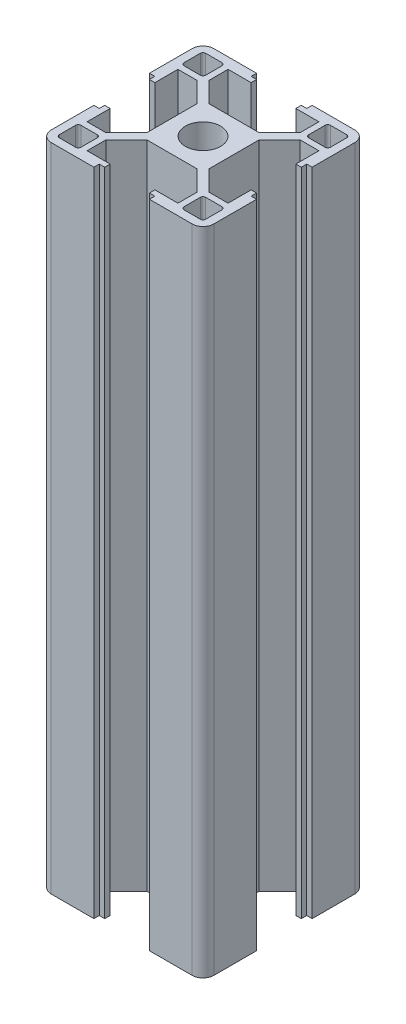
SolidWorks part; units mm, degrees
material "6061 Alloy"
ref_plane "Front Plane" through (0, 0, 0) normal (0, 0, 1) x (1, 0, 0)
ref_plane "Top Plane" through (0, 0, 0) normal (0, 1, 0) x (1, 0, 0)
ref_plane "Right Plane" through (0, 0, 0) normal (1, 0, 0) x (0, 0, -1)
sketch "Sketch1" plane through (0, 0, 0) normal (0, 1, 0) x (1, 0, 0)
  line L0 (-8.375, 13) -> (-4.125, 13)
  line L1 (-13, 15) -> (-4.125, 15)
  line L2 (-15, 13) -> (-15, 4.125)
  line L3 (-13, -15) -> (-4.125, -15)
  line L4 (15, 13) -> (15, 4.125)
  line L5 (-15, 15) -> (15, -15) construction
  line L6 (-15, -15) -> (15, 15) construction
  line L7 (-11.5, 11.5) -> (11.5, 11.5) construction
  line L8 (-11.5, 11.5) -> (-11.5, -11.5) construction
  line L9 (-11.5, -11.5) -> (11.5, -11.5) construction
  line L10 (11.5, 11.5) -> (11.5, -11.5) construction
  line L11 (-11.5, 11.5) -> (11.5, -11.5) construction
  line L12 (-11.5, -11.5) -> (11.5, 11.5) construction
  line L13 (-13.5, 13.5) -> (-9.5, 13.5)
  line L14 (-13.5, 13.5) -> (-13.5, 9.5)
  line L15 (-13.5, 9.5) -> (-9.5, 9.5)
  line L16 (-9.5, 13.5) -> (-9.5, 9.5)
  line L17 (-13.5, 13.5) -> (-9.5, 9.5) construction
  line L18 (-13.5, 9.5) -> (-9.5, 13.5) construction
  line L19 (13.5, 13.5) -> (9.5, 13.5)
  line L20 (13.5, 13.5) -> (13.5, 9.5)
  line L21 (13.5, 9.5) -> (9.5, 9.5)
  line L22 (9.5, 13.5) -> (9.5, 9.5)
  line L23 (13.5, 13.5) -> (9.5, 9.5) construction
  line L24 (13.5, 9.5) -> (9.5, 13.5) construction
  line L25 (13.5, -13.5) -> (9.5, -13.5)
  line L26 (13.5, -13.5) -> (13.5, -9.5)
  line L27 (13.5, -9.5) -> (9.5, -9.5)
  line L28 (9.5, -13.5) -> (9.5, -9.5)
  line L29 (13.5, -13.5) -> (9.5, -9.5) construction
  line L30 (13.5, -9.5) -> (9.5, -13.5) construction
  line L31 (-13.5, -13.5) -> (-9.5, -13.5)
  line L32 (-13.5, -13.5) -> (-13.5, -9.5)
  line L33 (-13.5, -9.5) -> (-9.5, -9.5)
  line L34 (-9.5, -13.5) -> (-9.5, -9.5)
  line L35 (-13.5, -13.5) -> (-9.5, -9.5) construction
  line L36 (-13.5, -9.5) -> (-9.5, -13.5) construction
  line L37 (0, 15) -> (0, 13) construction
  line L38 (-4.125, 15) -> (-4.125, 13)
  line L39 (4.125, 15) -> (4.125, 13)
  line L40 (4.125, 15) -> (13, 15)
  line L41 (-15, 15) -> (15, 15) construction
  line L42 (4.125, 13) -> (8.375, 13)
  line L43 (-15, 13) -> (15, 13) construction
  line L44 (8.375, 9.5064) -> (4.6186, 5.75)
  line L45 (-4.6186, -5.75) -> (4.6186, -5.75)
  line L46 (-8.375, 13) -> (-8.375, 9.5)
  line L47 (8.375, 13) -> (8.375, 9.5)
  line L48 (-8.375, 15) -> (-8.375, 13) construction
  line L49 (8.375, 15) -> (8.375, 13) construction
  line L50 (-5.75, -4.6186) -> (-5.75, 4.6186)
  line L51 (-4.6186, 5.75) -> (4.6186, 5.75)
  line L52 (5.75, -4.6186) -> (5.75, 4.6186)
  line L53 (-5.75, -5.75) -> (5.75, 5.75) construction
  line L54 (-5.75, 5.75) -> (5.75, -5.75) construction
  line L55 (-8.375, 9.5064) -> (-4.6186, 5.75)
  line L56 (-10.6314, 9.5) -> (-5.75, 4.6186)
  line L57 (-14.4343, 15.5657) -> (15.5657, -14.4343) construction
  line L58 (15, 4.125) -> (13, 4.125)
  line L59 (13, 8.375) -> (13, 4.125)
  line L60 (13, 8.375) -> (9.5, 8.375)
  line L61 (9.5064, 8.375) -> (5.75, 4.6186)
  line L62 (9.5064, -8.375) -> (5.75, -4.6186)
  line L63 (13, -8.375) -> (9.5, -8.375)
  line L64 (13, -4.125) -> (13, -8.375)
  line L65 (15, -4.125) -> (13, -4.125)
  line L66 (4.125, -15) -> (4.125, -13)
  line L67 (8.375, -13) -> (4.125, -13)
  line L68 (8.375, -13) -> (8.375, -9.5)
  line L69 (8.375, -9.5064) -> (4.6186, -5.75)
  line L70 (-8.375, -9.5064) -> (-4.6186, -5.75)
  line L71 (-8.375, -13) -> (-8.375, -9.5)
  line L72 (-4.125, -13) -> (-8.375, -13)
  line L73 (-4.125, -15) -> (-4.125, -13)
  line L74 (-15, -4.125) -> (-13, -4.125)
  line L75 (-13, -8.375) -> (-13, -4.125)
  line L76 (-13, -8.375) -> (-9.5, -8.375)
  line L77 (-9.5064, -8.375) -> (-5.75, -4.6186)
  line L78 (-9.5064, 8.375) -> (-5.75, 4.6186)
  line L79 (-13, 8.375) -> (-9.5, 8.375)
  line L80 (-13, 4.125) -> (-13, 8.375)
  line L81 (-15, 4.125) -> (-13, 4.125)
  line L82 (-15, -4.125) -> (-15, -13)
  line L83 (4.125, -15) -> (13, -15)
  line L84 (15, -4.125) -> (15, -13)
  circle A0 centre (0, 0) radius 3.25
  circle A1 centre (0, 0) radius 3.25
  circle A2 centre (0, 0) radius 3.25
  circle A3 centre (0, 0) radius 3.25
  arc A4 (-15, -13) -> (-13, -15) centre (-13, -13) ccw
  arc A5 (13, -15) -> (15, -13) centre (13, -13) ccw
  arc A6 (13, 15) -> (15, 13) centre (13, 13) cw
  arc A7 (-13, 15) -> (-15, 13) centre (-13, 13) ccw
  point P0 (0, 0)
  point P6 (0, 0)
  point P31 (0, 0)
  point P48 (-15.5657, 14.4343)
  point P49 (14.4343, -15.5657)
  point P60 (0, 5.75)
  point P102 (0, 0)
  dimension "D17" = 6.5
  dimension "D10" = 2
  dimension "D1" = 30
  dimension "D2" = 30
  dimension "D3" = 23
  dimension "D4" = 23
  dimension "D5" = 4
  dimension "D6" = 4
  dimension "D7" = 4
  dimension "D8" = 4
  dimension "D12" = 3.5
  dimension "D16" = 11.5
  dimension "D11" = 11.5
  dimension "D9" = 2
  dimension "D18" = 0.8
extrude "Boss-Extrude1" add sketch "Sketch1" along normal blind 120 contours L1 A7 L2 L81 L80 L79 L15 L14 L13 L16 L56 L50 L77 L76 L75 L74 L82 A4 L3 L73 L72 L71 L70 L45 L69 L68 L67 L66 L83 A5 L84 L65 L64 L63 L62 L52 L61 region at (-8.7993, 0, -11.2532)
sketch "Sketch2" plane through (0, 120, 0) normal (0, 1, 0) x (1, 0, 0)
  line L0 (15, 4.125) -> (14, 4.125)
  line L1 (-4.125, 15) -> (-5.125, 15)
  line L2 (-4.125, 15) -> (-4.125, 14)
  line L3 (-4.125, 14) -> (-5.125, 14)
  line L4 (-5.125, 15) -> (-5.125, 14)
  line L5 (4.125, 15) -> (5.125, 15)
  line L6 (4.125, 15) -> (4.125, 14)
  line L7 (4.125, 14) -> (5.125, 14)
  line L8 (5.125, 15) -> (5.125, 14)
  line L9 (15, 4.125) -> (15, 5.125)
  line L10 (15, 5.125) -> (14, 5.125)
  line L11 (14, 4.125) -> (14, 5.125)
  line L12 (15, -4.125) -> (14, -4.125)
  line L13 (15, -4.125) -> (15, -5.125)
  line L14 (15, -5.125) -> (14, -5.125)
  line L15 (14, -4.125) -> (14, -5.125)
  line L16 (4.125, -15) -> (4.125, -14)
  line L17 (4.125, -15) -> (5.125, -15)
  line L18 (5.125, -15) -> (5.125, -14)
  line L19 (4.125, -14) -> (5.125, -14)
  line L20 (-4.125, -15) -> (-4.125, -14)
  line L21 (-4.125, -15) -> (-5.125, -15)
  line L22 (-5.125, -15) -> (-5.125, -14)
  line L23 (-4.125, -14) -> (-5.125, -14)
  line L24 (-15, -4.125) -> (-14, -4.125)
  line L25 (-15, -4.125) -> (-15, -5.125)
  line L26 (-15, -5.125) -> (-14, -5.125)
  line L27 (-14, -4.125) -> (-14, -5.125)
  line L28 (-15, 4.125) -> (-14, 4.125)
  line L29 (-15, 4.125) -> (-15, 5.125)
  line L30 (-15, 5.125) -> (-14, 5.125)
  line L31 (-14, 4.125) -> (-14, 5.125)
  point P36 (0, 0)
  dimension "D1" = 1
  dimension "D2" = 1
  dimension "D3" = 1
  dimension "D4" = 1
  dimension "D5" = 4
extrude "Cut-Extrude1" cut sketch "Sketch2" against normal through all
fillet "Fillet1" radius 0.5 16 edges at (9.5, 60, 13.5) (-13.5, 60, 13.5) (-13.5, 60, -9.5) (9.5, 60, -9.5) (-13.5, 60, 9.5) (9.5, 60, 9.5) (9.5, 60, -13.5) (-13.5, 60, -13.5) (-9.5, 60, -13.5) (13.5, 60, -13.5) (13.5, 60, 9.5) (-9.5, 60, 9.5) (13.5, 60, 13.5) (-9.5, 60, 13.5) (-9.5, 60, -9.5) (13.5, 60, -9.5)
sketch "Sketch3" plane through (0, 0, -15) normal (0, 0, -1) x (-1, 0, 0)
  line L2 (-15, 120) -> (-15, 0) construction
  line L11 (-15, 51.9615) -> (-15, 0)
  line L12 (-15, 0) -> (15, 0)
  line L13 (15, 0) -> (-15, 51.9615)
  line L14 (-15, 60) -> (15, 60) construction
  line L15 (15, 120) -> (15, 0) construction
  line L27 (0, 94.0192) -> (0, 120)
  line L28 (0, 120) -> (15, 120)
  line L29 (15, 120) -> (0, 94.0192)
  line L30 (-5.125, 120) -> (-13, 120) construction
  line L31 (0, 94.0192) -> (-15, 102.6795)
  line L32 (-15, 102.6795) -> (-15, 120)
  line L33 (-15, 120) -> (0, 120)
  dimension "D1" = 30
  dimension "D2" = 60
  dimension "D3" = 30
  dimension "D4" = 90
extrude "Cut-Extrude2" [suppressed] cut sketch "Sketch3" against normal through all
equation "\"L\"= 385"
